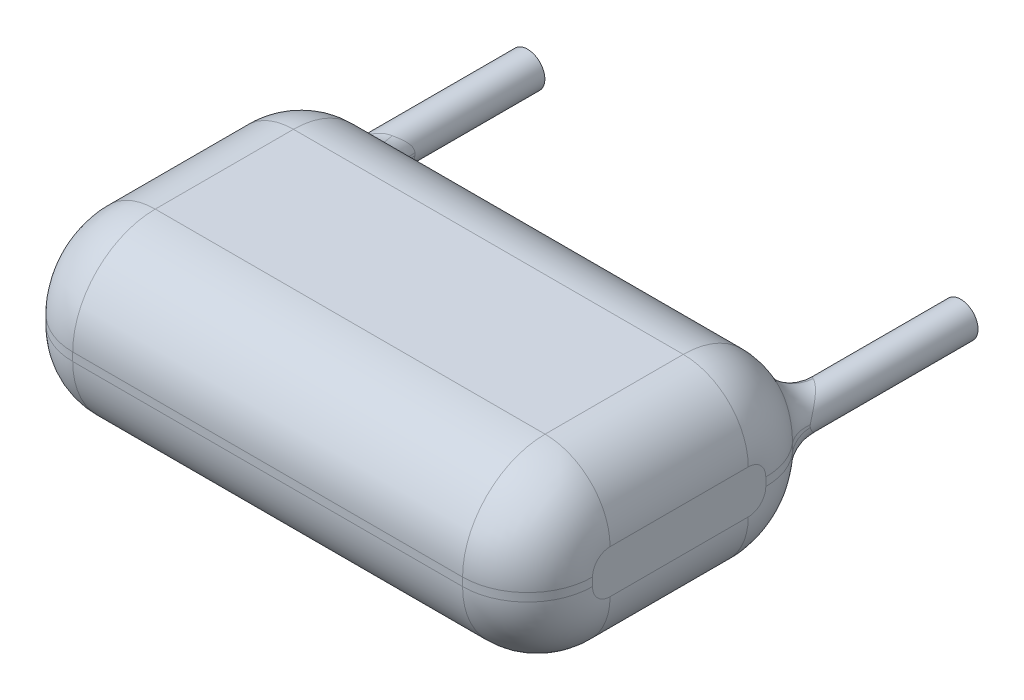
SolidWorks part; units mm, degrees
ref_plane "Plan de face" through (0, 0, 0) normal (0, 0, 1) x (1, 0, 0)
ref_plane "Plan de dessus" through (0, 0, 0) normal (0, 1, 0) x (1, 0, 0)
ref_plane "Plan de droite" through (0, 0, 0) normal (1, 0, 0) x (0, 0, -1)
sketch "Esquisse1" plane through (0, 0, 0) normal (1, 0, 0) x (0, 0, -1)
  line L5 (-6.0952, 2) -> (-2.9048, 2)
  line L6 (-8, 0.0952) -> (-8, -0.0952)
  line L7 (-6.0952, -2) -> (-2.9048, -2)
  line L8 (-1, 0.0952) -> (-1, -0.0952)
  line L9 (-8, 2) -> (-1, -2) construction
  line L10 (-8, -2) -> (-1, 2) construction
  arc A2 (-2.9048, -2) -> (-1, -0.0952) centre (-2.9048, -0.0952) ccw
  arc A4 (-8, -0.0952) -> (-6.0952, -2) centre (-6.0952, -0.0952) ccw
  arc A5 (-2.9048, 2) -> (-1, 0.0952) centre (-2.9048, 0.0952) cw
  arc A7 (-6.0952, 2) -> (-8, 0.0952) centre (-6.0952, 0.0952) ccw
  point P14 (-4.5, 0)
  dimension "D9" = 1.9048
  dimension "D7" = 7
  dimension "D8" = 4
  dimension "D1" = 1
extrude "Extrusion1" add sketch "Esquisse1" along normal mid plane 12
sketch "Esquisse3" plane through (0, 4, 1) normal (0, 0, -1) x (1, 0, 0)
  line L0 (-5, 4) -> (5, 4) construction
  circle A0 centre (-5, 4) radius 0.4
  circle A1 centre (5, 4) radius 0.4
  point P4 (0, 4)
  dimension "D1" = 10
fillet "Congé12" radius 1.5 16 edges at (-6, 0, 1) (-6, 1.4421, 1.5579) (-6, 2, 4.5) (-6, 1.4421, 7.4421) (-6, 0, 8) (-6, -1.4421, 7.4421) (-6, -2, 4.5) (-6, -1.4421, 1.5579) (6, 1.4421, 1.5579) (6, 0, 1) (6, -1.4421, 1.5579) (6, -2, 4.5) (6, -1.4421, 7.4421) (6, 0, 8) (6, 1.4421, 7.4421) (6, 2, 4.5)
extrude "Extrusion5" add sketch "Esquisse3" along normal blind 4 and the other way blind 1
fillet "Fillet1" radius 1 8 edges at (-4.987, 0.3998, 1.1069) (-4.6059, 0.0684, 1.0037) (4.9888, 0.3998, 1.1075) (5.3956, 0.0593, 1.2967) (4.987, -0.3998, 1.1069) (-4.9888, -0.3998, 1.1075)
equation "\"D9@Esquisse1\"= \"D8@Esquisse1\" / 2.1"
